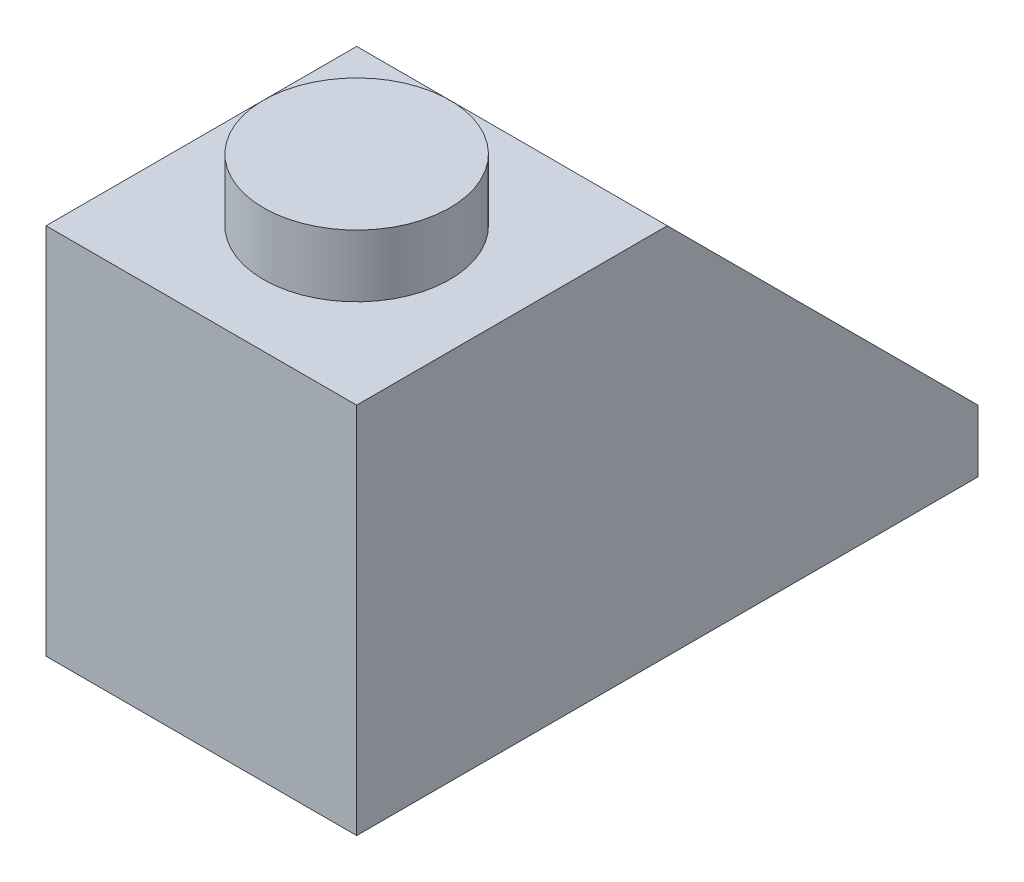
SolidWorks part; units mm, degrees
ref_plane "Front Plane" through (0, 0, 0) normal (0, 0, 1) x (1, 0, 0)
ref_plane "Top Plane" through (0, 0, 0) normal (0, 1, 0) x (1, 0, 0)
ref_plane "Right Plane" through (0, 0, 0) normal (1, 0, 0) x (0, 0, -1)
sketch "Sketch3" plane through (0, 0, 0) normal (1, 0, 0) x (0, 0, -1)
  line L0 (5, 6) -> (10, 1)
  line L1 (0, 0) -> (10, 0)
  line L2 (0, 0) -> (0, 6)
  line L3 (0, 6) -> (10, 6)
  line L4 (10, 0) -> (10, 6)
  line L5 (1, 5) -> (5, 5)
  line L6 (1, 5) -> (1, 0)
  line L7 (9, 0) -> (9, 1)
  line L8 (4, 6) -> (9, 1)
  line L10 (4, 6) -> (1, 6)
  line L11 (4, 6) -> (4, 7)
  point P8 (0, 0)
  point P16 (0, 0)
  dimension "D1" = 6
  dimension "D2" = 10
  dimension "D3" = 1
  dimension "D4" = 1
  dimension "D5" = 1
  dimension "D7" = 1
  dimension "D8" = 1
extrude "Boss-Extrude2" add sketch "Sketch3" along normal blind 5 contours L8 L3 L2 L1 L6 L5 | L8 L5 L6 L1 L7 | L3 L8 L7 L1 L4 L0 region at (0, 3, -7.4167) region at (0, 5.4448, -4.4448) region at (0, 2.2083, -4.3333)
extrude "Cut-Extrude1" cut sketch "Sketch3<5>" along normal blind 4 contours L8 L5 L6 L1 L7 region at (0, 2.2083, -4.3333)
sketch "Sketch3<5>" plane through (0, 0, 0) normal (1, 0, 0) x (0, 0, -1) same geometry as "Sketch3"
extrude "Boss-Extrude3" add sketch "Sketch3<6>" along normal blind 1 contours L8 L5 L6 L1 L7 region at (0, 2.2083, -4.3333)
sketch "Sketch3<6>" plane through (0, 0, 0) normal (1, 0, 0) x (0, 0, -1) same geometry as "Sketch3"
sketch "Sketch4" plane through (0, 6, 0) normal (0, 1, 0) x (1, 0, 0)
  line L0 (5, 0) -> (0, 0) construction
  line L1 (0, 0) -> (0, 5) construction
  circle A0 centre (2.5, 2.5) radius 1.5
  circle A1 centre (2.5, 2.5) radius 0.75
  point P5 (2.5, 0)
  point P8 (0, 2.5)
  dimension "D1" = 3
  dimension "D2" = 1.5
extrude "Cut-Extrude2" cut sketch "Sketch4" against normal up to next contours A1 region at (2.5, 6, -2.5)
extrude "Boss-Extrude6" add sketch "Sketch4<4>" along normal blind 1 contours A1 | A0 A1 region at (1.0424, 6, -2.5) region at (2.5, 6, -2.5)
sketch "Sketch4<4>" plane through (0, 6, 0) normal (0, 1, 0) x (1, 0, 0) same geometry as "Sketch4"
sketch "Sketch6" plane through (0, 5, 0) normal (0, -1, 0) x (-1, 0, 0)
  line L0 (-4, 5) -> (-1, 5) construction
  circle A0 centre (-2.5, 5) radius 1
  dimension "D1" = 2
extrude "Boss-Extrude7" add sketch "Sketch6" along normal up to surface (5 mm away) up to face at (2.5, 0, -5)
